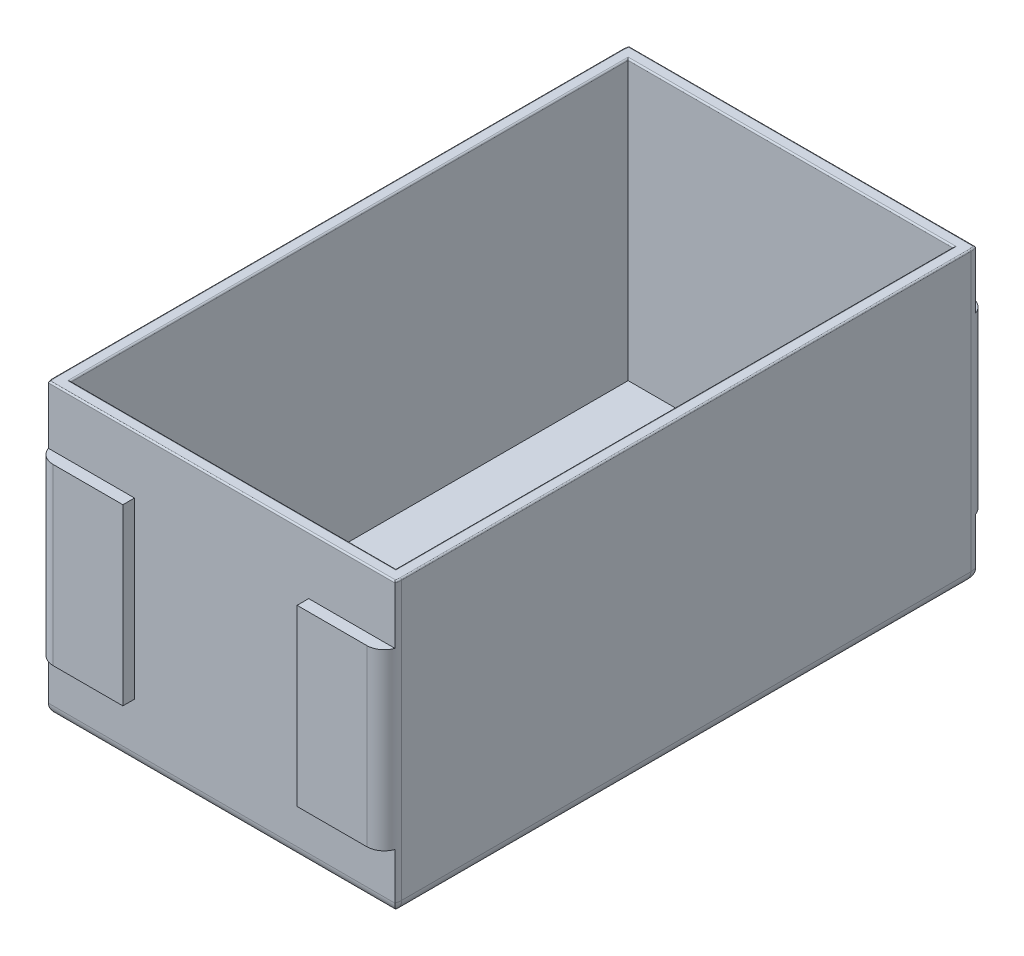
SolidWorks part; units mm, degrees
ref_plane "Front Plane" through (0, 0, 0) normal (0, 0, 1) x (1, 0, 0)
ref_plane "Top Plane" through (0, 0, 0) normal (0, 1, 0) x (1, 0, 0)
ref_plane "Right Plane" through (0, 0, 0) normal (1, 0, 0) x (0, 0, -1)
sketch "Sketch2" plane through (0, 0, 0) normal (0, 1, 0) x (1, 0, 0)
  line L1 (-30, -50) -> (30, -50)
  line L2 (-30, -50) -> (-30, 50)
  line L3 (-30, 50) -> (30, 50)
  line L4 (30, -50) -> (30, 50)
  line L5 (-30, -50) -> (30, 50) construction
  line L6 (-30, 50) -> (30, -50) construction
  point P0 (0, 0)
  dimension "D1" = 100
  dimension "D2" = 60
extrude "Boss-Extrude1" add sketch "Sketch2" along normal blind 50
sketch "Sketch3" plane through (0, 50, 0) normal (0, 1, 0) x (1, 0, 0)
  line L1 (-28, -48) -> (28, -48)
  line L2 (-28, -48) -> (-28, 48)
  line L3 (-28, 48) -> (28, 48)
  line L4 (28, -48) -> (28, 48)
  line L5 (-28, -48) -> (28, 48) construction
  line L6 (-28, 48) -> (28, -48) construction
  point P0 (0, 0)
  dimension "D1" = 96
  dimension "D2" = 56
extrude "Cut-Extrude1" cut sketch "Sketch3" against normal blind 48
sketch "Sketch4" plane through (0, 0, -50) normal (0, 0, -1) x (-1, 0, 0)
  line L0 (-30, 25) -> (30, 25) construction
  line L1 (-30, 50) -> (-30, 0) construction
  line L2 (30, 50) -> (30, 0) construction
  line L3 (-30, 40) -> (-30, 10)
  line L4 (-30, 40) -> (-15, 40)
  line L6 (-30, 10) -> (-15, 10)
  line L7 (-15, 40) -> (-15, 10)
  line L8 (-30, 25) -> (-15, 10) construction
  line L9 (-30, 25) -> (-15, 40) construction
  line L10 (0, 25) -> (0, 0) construction
  line L11 (30, 40) -> (30, 10)
  line L12 (30, 10) -> (15, 10)
  line L13 (15, 40) -> (15, 10)
  line L14 (30, 40) -> (15, 40)
  dimension "D1" = 15
  dimension "D2" = 30
extrude "Boss-Extrude2" add sketch "Sketch4" along normal blind 2
fillet "Fillet1" radius 3 2 edges at (30, 25, -52) (-30, 25, -52)
mirror "Mirror1" about plane through (0, 0, 0) normal (0, 0, 1) of "Fillet1", "Boss-Extrude2"
fillet "Fillet2" radius 2 4 edges at (0, 0, -50) (-30, 0, 0) (0, 0, 50) (30, 0, 0)
fillet "Fillet3" radius 0.25 12 edges at (-29.9568, 50, 49.5073) (-30, 50, 0) (-29.9568, 50, -49.5073) (0, 50, -50) (29.9568, 50, -49.5073) (30, 50, 0) (29.9568, 50, 49.5073) (0, 50, 50) (-28, 50, 0) (0, 50, 48) (28, 50, 0) (0, 50, -48)
